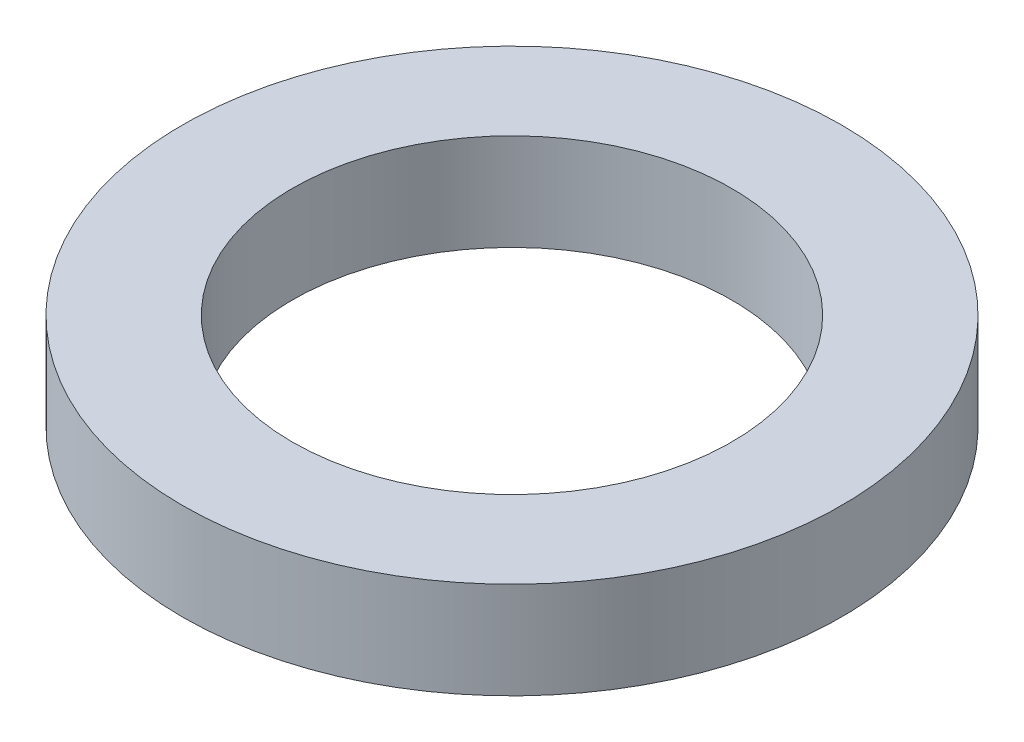
SolidWorks part; units mm, degrees
ref_plane "Front Plane" through (0, 0, 0) normal (0, 0, 1) x (1, 0, 0)
ref_plane "Top Plane" through (0, 0, 0) normal (0, 1, 0) x (1, 0, 0)
ref_plane "Right Plane" through (0, 0, 0) normal (1, 0, 0) x (0, 0, -1)
sketch "Sketch1" plane through (0, 0, 0) normal (0, 1, 0) x (1, 0, 0)
  circle A0 centre (0, 0) radius 75
  dimension "FLANGE_OD" = 150
extrude "Boss-Extrude1" add sketch "Sketch1" along normal blind 22
sketch "Sketch2" plane through (0, 0, 0) normal (0, 1, 0) x (1, 0, 0)
  circle A0 centre (0, 0) radius 50
  dimension "BORE_D" = 100
extrude "Cut-Extrude1" cut sketch "Sketch2" along normal through all
sketch "Sketch3" plane through (0, 22, 0) normal (0, 1, 0) x (1, 0, 0)
  circle A0 centre (0, 0) radius 30.4308 construction
  circle A1 centre (-30.4308, 0) radius 4.1758
  dimension "BOLT_D" = 8.3517
  dimension "BOLT_PCD" = 60.8616
extrude "Cut-Extrude2" cut sketch "Sketch3" against normal blind 20.4054 rebuild error yes
pattern_circular "CirPattern1" count 3 over 360 rebuild error yes
